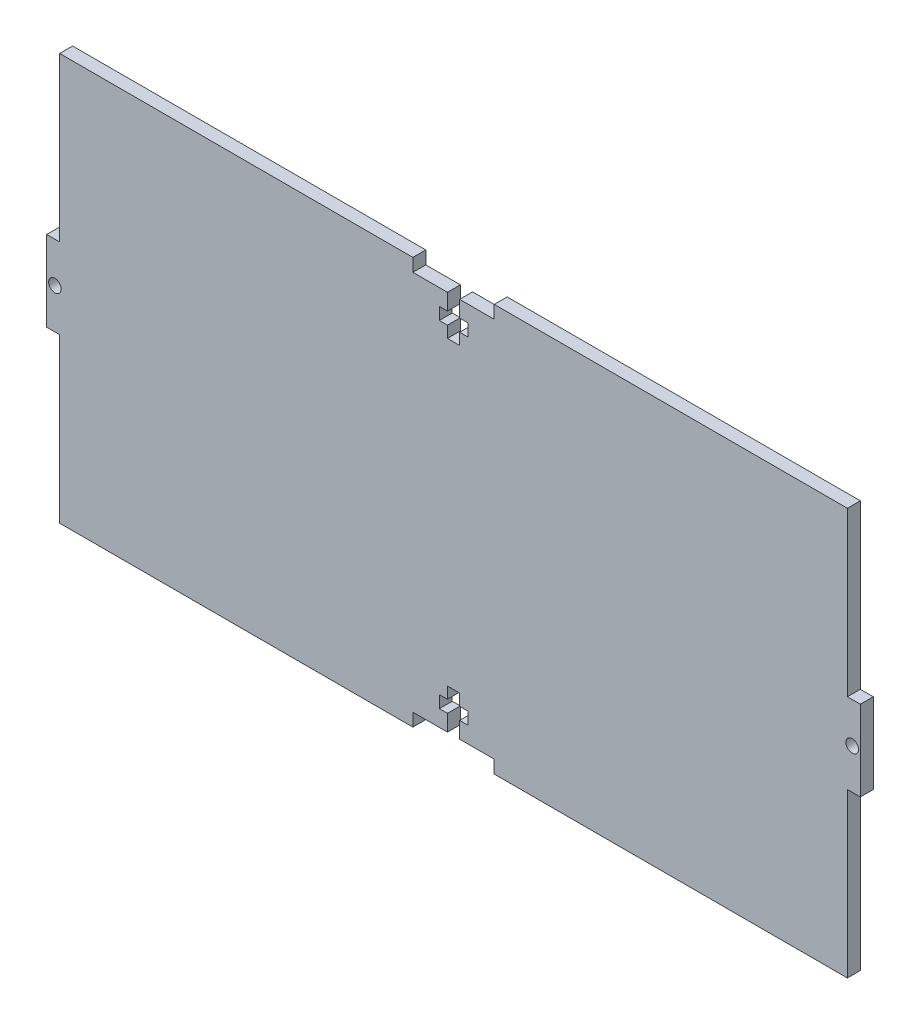
SolidWorks part; units mm, degrees
ref_plane "Front Plane" through (0, 0, 0) normal (0, 0, 1) x (1, 0, 0)
ref_plane "Top Plane" through (0, 0, 0) normal (0, 1, 0) x (1, 0, 0)
ref_plane "Right Plane" through (0, 0, 0) normal (1, 0, 0) x (0, 0, -1)
sketch "Sketch1" plane through (0, 0, 0) normal (0, 0, 1) x (1, 0, 0)
  line L0 (0, 40) -> (0, -40) construction
  line L5 (-100, -50) -> (100, 50) construction
  line L6 (-100, 50) -> (100, -50) construction
  line L7 (-100, 0) -> (100, 0) construction
  line L32 (-100, 50) -> (100, 50)
  line L35 (100, 50) -> (100, -50)
  line L36 (100, -50) -> (-100, -50)
  line L37 (-100, -50) -> (-100, 50)
  point P0 (0, 0)
  dimension "D1" = 200
  dimension "D2" = 100
extrude "Boss-Extrude2" add sketch "Sketch1" along normal blind 3.18
sketch "Sketch2" plane through (0, 0, 3.18) normal (0, 0, 1) x (1, 0, 0)
  line L0 (0, -50) -> (0, 50) construction
  line L1 (-123.0225, 0) -> (147.0753, 0) construction
  line L2 (100, 50) -> (-100, 50) construction
  line L4 (-10, 50) -> (-10, 46.82)
  line L5 (-10, 46.82) -> (-1.5, 46.82)
  line L6 (10, 50) -> (10, 46.82)
  line L7 (1.5, 46.82) -> (10, 46.82)
  line L9 (-1.5, 46.82) -> (-1.5, 42.82)
  line L10 (-1.5, 37) -> (1.5, 37)
  line L11 (1.5, 46.82) -> (1.5, 42.82)
  line L12 (-3.5, 42.82) -> (-1.5, 42.82)
  line L13 (-3.5, 42.82) -> (-3.5, 39.82)
  line L14 (-3.5, 39.82) -> (-1.5, 39.82)
  line L15 (3.5, 42.82) -> (3.5, 39.82)
  line L16 (1.5, 42.82) -> (3.5, 42.82)
  line L17 (-1.5, 39.82) -> (-1.5, 37)
  line L18 (1.5, 39.82) -> (1.5, 37)
  line L19 (1.5, 39.82) -> (3.5, 39.82)
  line L20 (-10, 50) -> (10, 50)
  line L21 (-100, -50) -> (100, -50) construction
  line L22 (-100, 50) -> (-100, -50) construction
  line L23 (-100, 9.875) -> (-96.82, 9.875)
  line L24 (-100, 9.875) -> (-100, 50)
  line L25 (-100, 50) -> (-96.82, 50)
  line L26 (-96.82, 9.875) -> (-96.82, 50)
  line L28 (-100, -9.875) -> (-96.82, -9.875)
  line L29 (-100, -9.875) -> (-100, -50)
  line L30 (-100, -50) -> (-96.82, -50)
  line L31 (-96.82, -9.875) -> (-96.82, -50)
  circle A0 centre (-98, 0) radius 1.55
  dimension "D11" = 3.1
  dimension "D12" = 2
  dimension "D1" = 4
  dimension "D2" = 3
  dimension "D3" = 3
  dimension "D4" = 20
  dimension "D5" = 7
  dimension "D6" = 3.18
  dimension "D7" = 13
  dimension "D8" = 19.75
  dimension "D9" = 3.18
  dimension "D10" = 3.18
extrude "Cut-Extrude1" cut sketch "Sketch2" against normal through all
mirror "Mirror1" about plane through (0, 0, 0) normal (0, 1, 0) of "Cut-Extrude1"
mirror "Mirror2" about plane through (0, 0, 0) normal (1, 0, 0) of "Cut-Extrude1"
